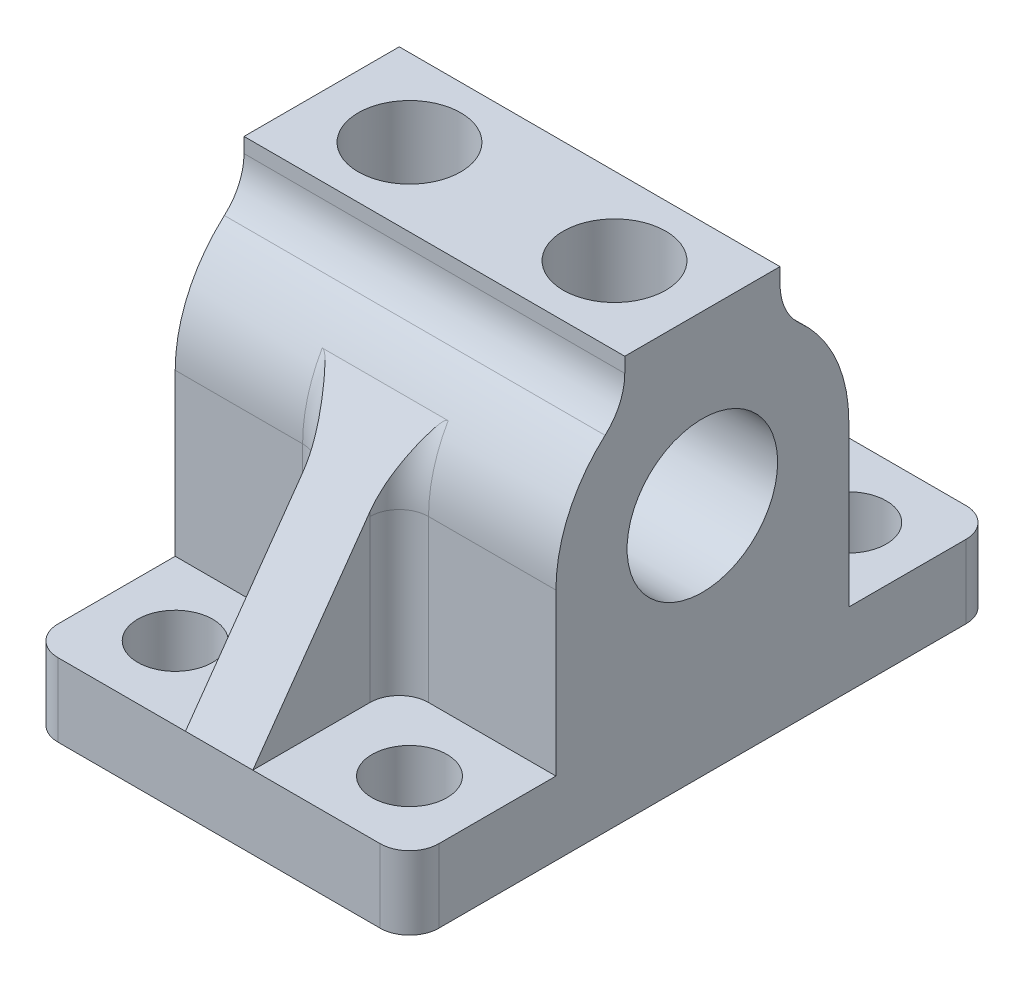
SolidWorks part; units mm, degrees
material "PLA2"
ref_plane "Front Plane" through (0, 0, 0) normal (0, 0, 1) x (1, 0, 0)
ref_plane "Top Plane" through (0, 0, 0) normal (0, 1, 0) x (1, 0, 0)
ref_plane "Right Plane" through (0, 0, 0) normal (1, 0, 0) x (0, 0, -1)
sketch "Sketch1" plane through (0, 0, 0) normal (1, 0, 0) x (0, 0, -1)
  line L0 (0, 0) -> (27506.0917, 0) construction
  line L1 (0.3138, 19.05) -> (27506.4055, 19.05) construction
  line L2 (0, 29.21) -> (0, 0) construction
  line L3 (12.7, 19.05) -> (-12.7, 19.05)
  line L4 (-12.7, 19.05) -> (-12.7, 22.225)
  line L5 (-12.7, 22.225) -> (-6.35, 22.225)
  line L6 (-6.35, 22.225) -> (-6.35, 29.21)
  line L7 (0, 29.21) -> (0, 35.56) construction
  line L8 (6.35, 22.225) -> (6.35, 29.21)
  line L9 (12.7, 22.225) -> (6.35, 22.225)
  line L10 (12.7, 19.05) -> (12.7, 22.225)
  circle A0 centre (0, 29.21) radius 3.2639
  arc A1 (6.35, 29.21) -> (-6.35, 29.21) centre (0, 29.21) ccw
  point P19 (0, 19.05)
  dimension "D2" = 6.5278
  dimension "D4" = 12.7
  dimension "D7" = 3.0861
  dimension "D1" = 19.05
  dimension "D3" = 29.21
  dimension "D5" = 3.175
  dimension "D6" = 6.35
extrude "Boss-Extrude1" add sketch "Sketch1" along normal mid plane 16.51
sketch "Sketch2" plane through (0, 0, 0) normal (1, 0, 0) x (0, 0, -1)
  line L0 (0, 32.4739) -> (0, 25.9461) construction
  line L1 (-5.4993, 32.385) -> (-12.7, 22.225)
  line L2 (-6.35, 22.225) -> (-12.7, 22.225) construction
  line L3 (-12.7, 22.225) -> (-5.4993, 22.225)
  line L4 (-5.4993, 22.225) -> (-5.4993, 32.385)
  line L5 (5.4993, 22.225) -> (5.4993, 32.385)
  line L6 (12.7, 22.225) -> (5.4993, 22.225)
  line L7 (5.4993, 32.385) -> (12.7, 22.225)
  circle A0 centre (0, 29.21) radius 3.2639 construction
  arc A1 (6.35, 29.21) -> (-6.35, 29.21) centre (0, 29.21) ccw construction
  dimension "D1" = 10.16
extrude "Boss-Extrude2" add sketch "Sketch2" along normal mid plane 2.921
sketch "Sketch3" plane through (0, 22.225, 0) normal (0, 1, 0) x (1, 0, 0)
  line L0 (-8.255, 0) -> (8.255, 0) construction
  line L1 (-8.255, 6.35) -> (-8.255, -6.35) construction
  line L2 (8.255, -6.35) -> (8.255, 6.35) construction
  line L3 (0, 12.7) -> (0, -12.7) construction
  line L4 (1.4605, 12.7) -> (-1.4605, 12.7) construction
  line L5 (1.4605, -12.7) -> (-1.4605, -12.7) construction
  circle A0 centre (-5.08, 9.525) radius 1.6256
  circle A1 centre (5.08, 9.525) radius 1.6256
  circle A2 centre (5.08, -9.525) radius 1.6256
  circle A3 centre (-5.08, -9.525) radius 1.6256
  dimension "D1" = 3.2512
  dimension "D2" = 10.16
  dimension "D3" = 19.05
extrude "Cut-Extrude1" cut sketch "Sketch3" against normal through all
sketch "Sketch4" plane through (8.255, 0, 0) normal (1, 0, 0) x (0, 0, -1)
  line L0 (3.3655, 34.5948) -> (-3.3655, 34.5948)
  arc A0 (6.35, 29.21) -> (-6.35, 29.21) centre (0, 29.21) ccw construction
  arc A1 (3.3655, 34.5948) -> (-3.3655, 34.5948) centre (0, 29.21) ccw
  dimension "D1" = 6.731
extrude "Cut-Extrude2" cut sketch "Sketch4" against normal through all
sketch "Sketch6" plane through (0, 34.5948, 0) normal (0, 1, 0) x (1, 0, 0)
  line L4 (8.255, -3.3655) -> (8.255, 3.3655)
  line L5 (8.255, 3.3655) -> (-8.255, 3.3655)
  line L6 (-8.255, 3.3655) -> (-8.255, -3.3655)
  line L7 (-8.255, -3.3655) -> (8.255, -3.3655)
  line L8 (8.255, -3.3655) -> (8.255, 3.3655)
  line L9 (8.255, 3.3655) -> (-8.255, 3.3655)
  line L10 (-8.255, 3.3655) -> (-8.255, -3.3655)
  line L11 (-8.255, -3.3655) -> (8.255, -3.3655)
  dimension "D1" = 0
extrude "Boss-Extrude3" add sketch "Sketch6" along normal blind 1.905
sketch "Sketch5" plane through (0, 36.4998, 0) normal (0, 1, 0) x (1, 0, 0)
  line L0 (0, 12.7) -> (0, -12.7) construction
  line L1 (1.4605, 12.7) -> (-1.4605, 12.7) construction
  line L2 (1.4605, -12.7) -> (-1.4605, -12.7) construction
  line L3 (-8.255, 0) -> (8.255, 0) construction
  line L6 (-8.255, 3.3655) -> (-8.255, -3.3655) construction
  line L7 (8.255, -3.3655) -> (8.255, 3.3655) construction
  circle A0 centre (-4.445, 0) radius 2.2225
  circle A1 centre (4.445, 0) radius 2.2225
  dimension "D1" = 4.445
  dimension "D2" = 8.89
extrude "Cut-Extrude3" cut sketch "Sketch5" against normal blind 6.35
fillet "Fillet1" radius 1.27 12 edges at (-1.4605, 30.8535, 6.1336) (1.4605, 30.8535, 6.1336) (-1.4605, 30.8535, -6.1336) (1.4605, 30.8535, -6.1336) (-1.4605, 25.7175, 6.35) (1.4605, 25.7175, 6.35) (-1.4605, 25.7175, -6.35) (1.4605, 25.7175, -6.35) (-8.255, 20.6375, -12.7) (8.255, 20.6375, -12.7) (-8.255, 20.6375, 12.7) (8.255, 20.6375, 12.7)
fillet "Fillet2" radius 2.54 2 edges at (0, 34.5948, -3.3655) (0, 34.5948, 3.3655)
